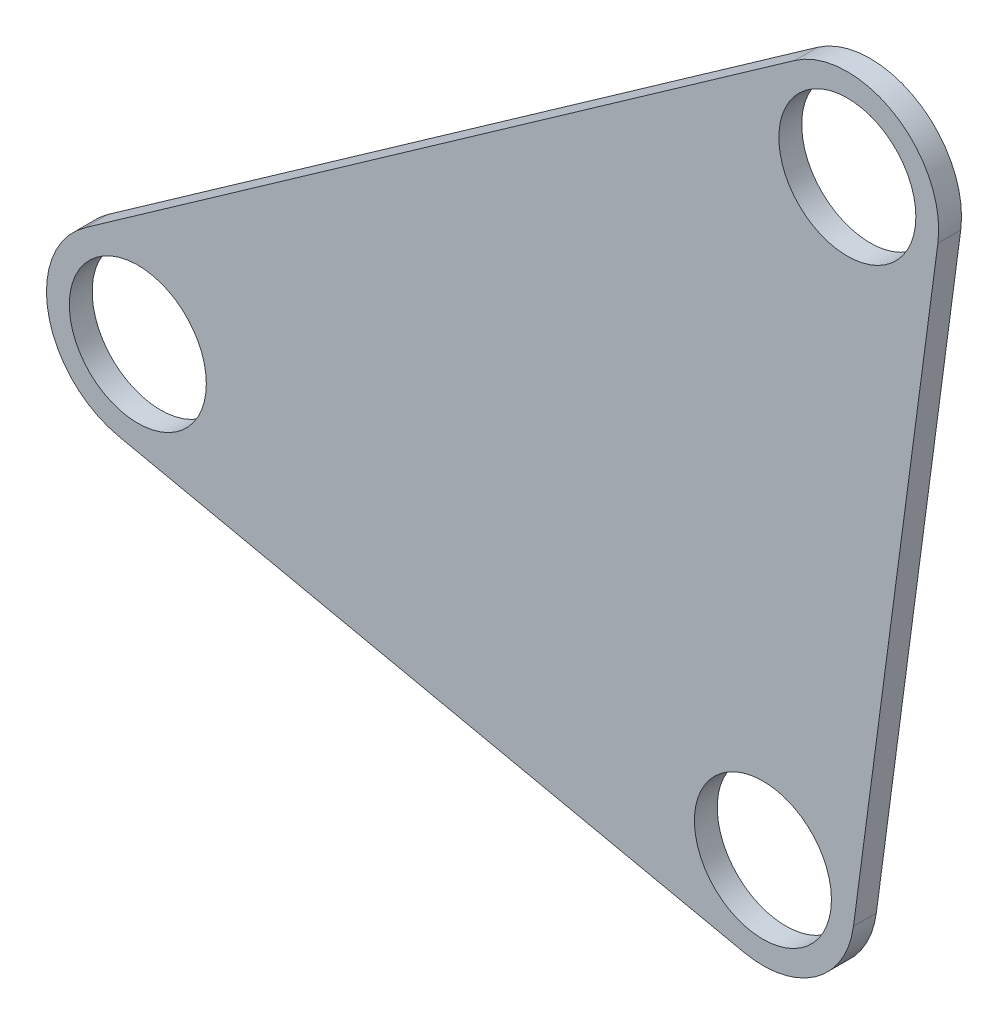
SolidWorks part; units mm, degrees
ref_plane "Plan de face" through (0, 0, 0) normal (0, 0, 1) x (1, 0, 0)
ref_plane "Plan de dessus" through (0, 0, 0) normal (0, 1, 0) x (1, 0, 0)
ref_plane "Plan de droite" through (0, 0, 0) normal (1, 0, 0) x (0, 0, -1)
sketch "Esquisse1" plane through (0, 0, 0) normal (0, 0, 1) x (1, 0, 0)
  line L2 (-59.9807, -3.9008) -> (-32.6051, -9.781)
  line L5 (-27.8001, -6.3983) -> (-24.1033, 21.3566)
  line L7 (-61.4433, 3.2808) -> (-30.3709, 25.1555)
  circle A6 centre (-28.0683, 21.8847) radius 3
  circle A7 centre (-31.7651, -5.8702) radius 3
  circle A8 centre (-59.1407, 0.01) radius 3
  arc A9 (-24.1033, 21.3566) -> (-30.3709, 25.1555) centre (-28.0683, 21.8847) ccw
  arc A10 (-32.6051, -9.781) -> (-27.8001, -6.3983) centre (-31.7651, -5.8702) ccw
  arc A11 (-59.9807, -3.9008) -> (-61.4433, 3.2808) centre (-59.1407, 0.01) cw
  point P4 (-45.4529, -2.9301)
  point P9 (-29.9167, 8.0073)
  point P17 (-43.6045, 10.9473)
  dimension "D1" = 6
  dimension "D2" = 6
  dimension "D3" = 6
base flange "Tôle de base pliée1" sketch "Esquisse1" thickness 1 reverse thickness direction yes parameters "D1"=0.7366
sketch "Lignes de pliage1" [suppressed] plane through (0, 0, 0) normal (0, 1, 0) x (1, 0, 0)
sketch "Cube de visualisation1" [suppressed] plane through (0, 0, 0) normal (0, 1, 0) x (1, 0, 0)
sheet metal parameters "Tôlerie1" thickness 1 parameters "D1"=0.7366
flat pattern "Etat déplié1" [suppressed]
sketch "Lignes de pliage2" plane through (0, 0, 0) normal (0, 1, 0) x (1, 0, 0)
sketch3d "Cube de visualisation2" [suppressed]
  line L0 (2.791, 32.0405, 0) -> (37.9881, 24.4803, 0) construction
  line L1 (-4.7508, -3.0708, 0) -> (30.4463, -10.631, 0) construction
  line L2 (2.791, 32.0405, 0) -> (-4.7508, -3.0708, 0) construction
  line L3 (37.9881, 24.4803, 0) -> (30.4463, -10.631, 0) construction
